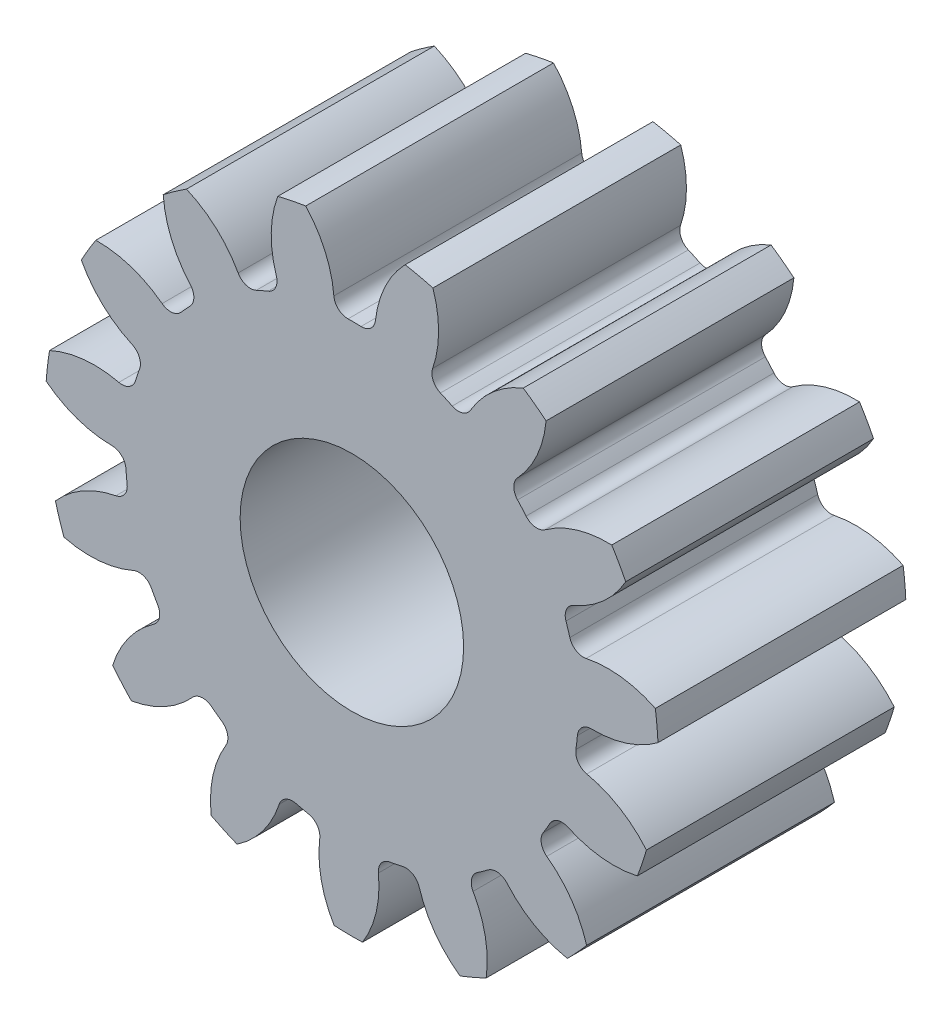
SolidWorks part; units mm, degrees
material "Delrin 2700 NC010, Low Viscosity Acetal Copolymer (SS)"
ref_plane "Front" through (0, 0, 0) normal (0, 0, 1) x (1, 0, 0)
ref_plane "Top" through (0, 0, 0) normal (0, 1, 0) x (1, 0, 0)
ref_plane "Right" through (0, 0, 0) normal (1, 0, 0) x (0, 0, -1)
sketch "Sketch3" plane through (0, 0, 0) normal (0, 0, 1) x (1, 0, 0)
  circle A0 centre (0, 0) radius 21.59
  dimension "od" = 43.18
extrude "gearBody" add sketch "Sketch3" along normal blind 17.4625
sketch "Sketch2" plane through (0, 0, 0) normal (0, 0, 1) x (1, 0, 0)
  line L0 (0, 0) -> (17.0393, 7.0579) construction
  line L1 (22.0105, -8.0941) -> (0, 0) construction
  line L2 (0, 0) -> (36.3143, 0) construction
  line L3 (19.0486, -0.229) -> (18.5878, -4.1711) construction
  line L5 (18.8182, -2.2) -> (0, 0) construction
  line L7 (0, 0) -> (18.4432, 0) construction
  arc A0 (18.4395, -0.3701) -> (18.0276, -3.8932) centre (0, 0) ccw construction
  arc A1 (21.5666, 1.0048) -> (20.7532, -5.9524) centre (0, 0) ccw construction
  arc A2 (19.0486, -0.229) -> (18.5878, -4.1711) centre (0, 0) ccw construction
  arc A3 (15.7838, -2.3046) -> (15.8898, -1.3984) centre (0, 0) ccw
  arc A4 (22.0105, -8.0941) -> (16.5506, -3.4102) centre (14.9518, -10.798) ccw
  arc A5 (22.0105, -8.0941) -> (23.2839, 2.7987) centre (0, 0) ccw
  arc A6 (23.2839, 2.7987) -> (16.8909, -0.4995) centre (17.0393, 7.0579) cw
  arc A7 (15.8898, -1.3984) -> (16.8909, -0.4995) centre (16.8715, -1.4848) cw
  arc A8 (16.5506, -3.4102) -> (15.7838, -2.3046) centre (16.759, -2.4469) cw
  point P6 (23.2839, 2.7987)
  point P22 (22.0105, -8.0941)
  dimension "baseDia" = 36.8864
  dimension "od" = 43.18
  dimension "pd" = 38.1
  dimension "rd" = 31.9024
  dimension "rFillet" = 0.9855
  dimension "pointX" = 23.2839
  dimension "pointY" = 2.7987
  dimension "CTT" = 3.9421
  dimension "flankCenterAngle" = 22.5
extrude "toothCut" cut sketch "Sketch2" along normal through all
pattern_circular "CirPattern1" count 15 over 360 about axis through (0, 0, 17.4625) along (0, 0, -1) of "toothCut"
sketch "hub1Dia" plane through (0, 0, 0) normal (0, 0, -1) x (-1, 0, 0)
  circle A0 centre (0, 0) radius 12.7
  dimension "hub1Dia" = 25.4
sketch "hub2Dia" plane through (0, 0, 17.4625) normal (0, 0, 1) x (1, 0, 0)
  circle A0 centre (0, 0) radius 12.7
  dimension "hub2dia" = 25.4
sketch "boreDia" plane through (0, 0, 0) normal (0, 0, 1) x (1, 0, 0)
  circle A0 centre (0, 0) radius 7.874
  dimension "boreDia" = 15.748
extrude "bore" cut sketch "boreDia" against normal mid plane 25400
